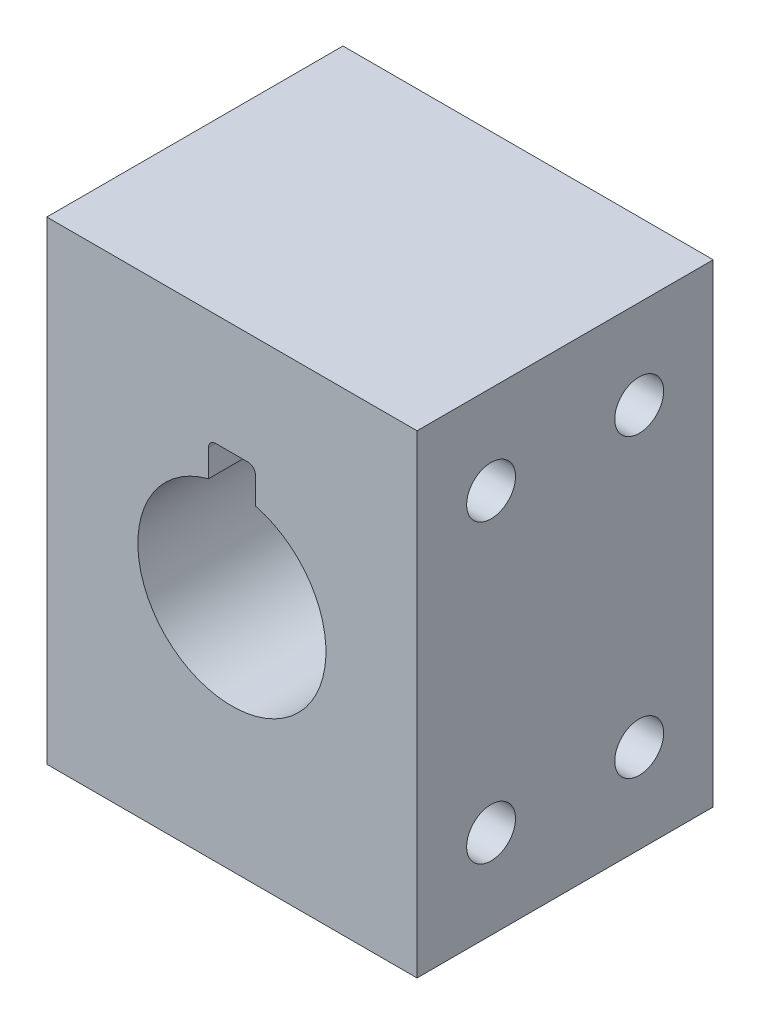
SolidWorks part; units mm, degrees
material "AISI 304"
ref_plane "Front Plane" through (0, 0, 0) normal (0, 0, 1) x (1, 0, 0)
ref_plane "Top Plane" through (0, 0, 0) normal (0, 1, 0) x (1, 0, 0)
ref_plane "Right Plane" through (0, 0, 0) normal (1, 0, 0) x (0, 0, -1)
sketch "Sketch1" plane through (0, 0, 0) normal (0, 0, 1) x (1, 0, 0)
  line L1 (0, 0) -> (-25, 0)
  line L2 (0, 0) -> (0, 32)
  line L3 (0, 32) -> (-25, 32)
  line L4 (-25, 0) -> (-25, 32)
  dimension "D1" = 25
  dimension "D2" = 32
extrude "Boss-Extrude1" add sketch "Sketch1" along normal blind 20
ref_plane "Plane1" through (-12.5, 0, 0) normal (-1, 0, 0) x (0, 0, 1)
sketch "Sketch2" plane through (0, 0, 20) normal (0, 0, 1) x (1, 0, 0)
  line L0 (0, 32) -> (-25, 32) construction
  line L1 (-25, 32) -> (-25, 0) construction
  line L3 (-14.0875, 24.4625) -> (-10.9125, 24.4625)
  line L4 (-14.0875, 24.4625) -> (-14.0875, 20.7625)
  line L5 (-14.0875, 20.7625) -> (-10.9125, 20.7625)
  line L6 (-10.9125, 24.4625) -> (-10.9125, 20.7625)
  circle A0 centre (-12.5, 16) radius 6.35
  point P5 (-12.5, 32)
  point P9 (-25, 16)
  point P12 (-12.5, 20.7625)
  dimension "D1" = 12.7
  dimension "D2" = 3.7
  dimension "D3" = 3.175
  dimension "D4" = 4.7625
extrude "Cut-Extrude1" cut sketch "Sketch2" against normal through all contours L4 A0 L6 L5 | A0 L6 L3 L4 | L6 A0 L4 L5 region at (-12.5, 23.372, 20) region at (-12.5, 21.524, 20) region at (-12.5, 15.7811, 20)
hole_wizard "M4x0.7 Tapped Hole1" positions "Sketch3" profile "Sketch4" tap size "M4x0.7" standard "ANSI Metric"
sketch "Sketch3" plane through (-25, 0, 0) normal (-1, 0, 0) x (0, 0, 1)
  line L1 (5, 26) -> (15, 26)
  line L2 (5, 26) -> (5, 6)
  line L3 (5, 6) -> (15, 6)
  line L4 (15, 26) -> (15, 6)
  line L5 (0, 32) -> (0, 0) construction
  line L6 (20, 32) -> (0, 32) construction
  point P1 (5, 26)
  point P2 (15, 6)
  point P153 (5, 6)
  point P154 (15, 26)
  point P168 (0, 16)
  point P169 (5, 16)
  point P170 (10, 26)
  point P173 (10, 32)
  dimension "D1" = 10
  dimension "D2" = 20
sketch "Sketch4" plane through (-25, 26, 5) normal (0, 1, 0) x (0, 0, 1)
  line L0 (0, 0) -> (0, 7.9914)
  line L1 (0, 7.9914) -> (1.65, 7)
  line L2 (1.65, 7) -> (1.65, 0)
  line L5 (1.65, 0) -> (0, 0)
  line L10 (0, 7.9914) -> (-1.65, 7) construction
  line L11 (0, -6.35) -> (0, 107.95) construction
  dimension "Tap Drill Dia." = 3.3
  dimension "Tap Drill Depth" = 7
  dimension "Drill Angle" = 118
mirror "Mirror1" about plane through (-12.5, 0, 0) normal (-1, 0, 0) of "M4x0.7 Tapped Hole1"
ref_axis "Axis1" through (-12.5, 16, 0) along (0, 0, 1)
fillet "Fillet1" radius 0.5 2 edges at (-10.9125, 24.4625, 10) (-14.0875, 24.4625, 10)
